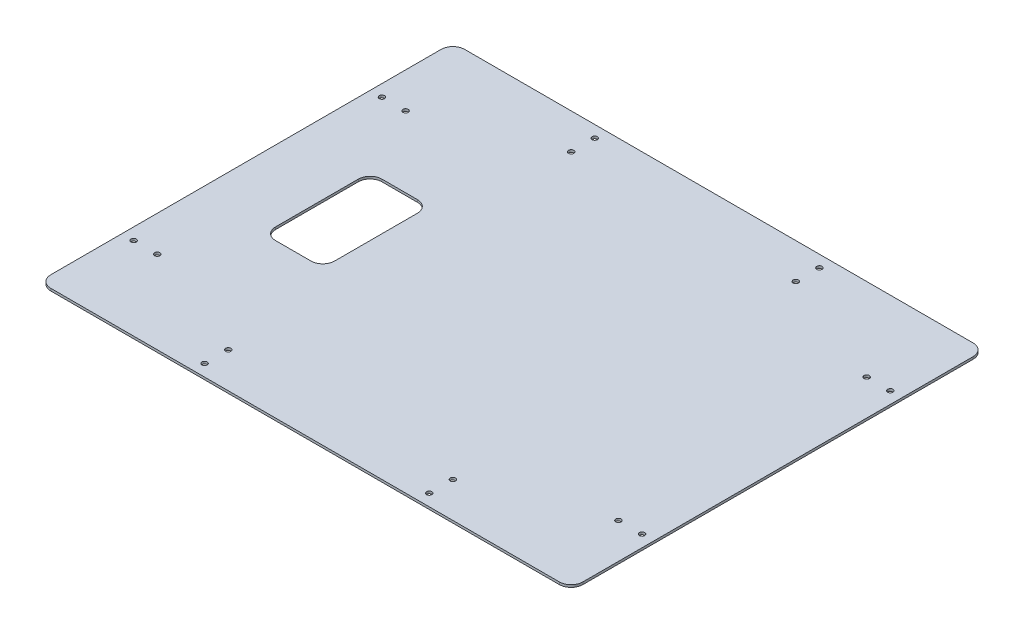
SolidWorks part; units mm, degrees
material "1060 Alloy"
ref_plane "Front Plane" through (0, 0, 0) normal (0, 0, 1) x (1, 0, 0)
ref_plane "Top Plane" through (0, 0, 0) normal (0, 1, 0) x (1, 0, 0)
ref_plane "Right Plane" through (0, 0, 0) normal (1, 0, 0) x (0, 0, -1)
sketch "Sketch5" plane through (0, 0, 0) normal (0, 1, 0) x (1, 0, 0)
  line L1 (0, 0) -> (450, 0)
  line L2 (0, 0) -> (0, 350)
  line L3 (0, 350) -> (450, 350)
  line L4 (450, 0) -> (450, 350)
  dimension "D1" = 450
  dimension "D2" = 350
extrude "Boss-Extrude1" add sketch "Sketch5" along normal blind 2 contours L2 L3 L4 L1
fillet "Fillet1" radius 10 4 edges at (0, 1, -350) (450, 1, -350) (450, 1, 0) (0, 1, 0)
sketch "Sketch6" plane through (0, 2, 0) normal (0, 1, 0) x (1, 0, 0)
  line L1 (70, 220) -> (100, 220)
  line L2 (60, 210) -> (60, 140)
  line L3 (70, 130) -> (100, 130)
  line L4 (110, 210) -> (110, 140)
  line L5 (0, 10) -> (0, 340) construction
  line L6 (85, 220) -> (85, 350) construction
  line L7 (10, 350) -> (440, 350) construction
  line L8 (85, 130) -> (85, 0) construction
  line L9 (10, 0) -> (440, 0) construction
  arc A0 (60, 140) -> (70, 130) centre (70, 140) ccw
  arc A1 (100, 130) -> (110, 140) centre (100, 140) ccw
  arc A2 (100, 220) -> (110, 210) centre (100, 210) cw
  arc A3 (70, 220) -> (60, 210) centre (70, 210) ccw
  dimension "D1" = 10
  dimension "D2" = 50
  dimension "D3" = 90
  dimension "D5" = 60
extrude "Cut-Extrude1" cut sketch "Sketch6" against normal through all
sketch "Sketch7" plane through (0, 2, 0) normal (0, 1, 0) x (1, 0, 0)
  line L0 (10, 0) -> (440, 0) construction
  line L1 (0, 10) -> (0, 340) construction
  line L2 (130, 30) -> (130, 10) construction
  line L3 (10, 70) -> (30, 70) construction
  line L4 (225, 350) -> (225, 0) construction
  line L5 (10, 350) -> (440, 350) construction
  line L6 (0, 175) -> (450, 175) construction
  line L7 (450, 10) -> (450, 340) construction
  point P0 (130, 10)
  point P1 (130, 30)
  point P2 (10, 70)
  point P3 (30, 70)
  point P20 (320, 10)
  point P21 (320, 30)
  point P22 (420, 70)
  point P23 (440, 70)
  point P24 (440, 280)
  point P25 (420, 280)
  point P26 (320, 340)
  point P27 (320, 320)
  point P28 (130, 340)
  point P29 (130, 320)
  point P30 (30, 280)
  point P31 (10, 280)
  dimension "D1" = 10
  dimension "D2" = 20
  dimension "D3" = 10
  dimension "D4" = 20
  dimension "D5" = 130
  dimension "D6" = 70
hole_wizard "M4 Clearance Hole1" positions "Sketch7" profile "Sketch8" hole size "M4" standard "ANSI Metric" end condition through all
sketch "Sketch8" plane through (130, 2, -10) normal (1, 0, 0) x (0, 0, 1)
  line L0 (0, 0) -> (0, 2)
  line L1 (0, 2) -> (2.25, 2)
  line L2 (2.25, 2) -> (2.25, 0)
  line L5 (2.25, 0) -> (0, 0)
  line L11 (0, -6.35) -> (0, 107.95) construction
  dimension "Thru Hole Dia." = 4.5
  dimension "Thru Hole Depth" = 2
